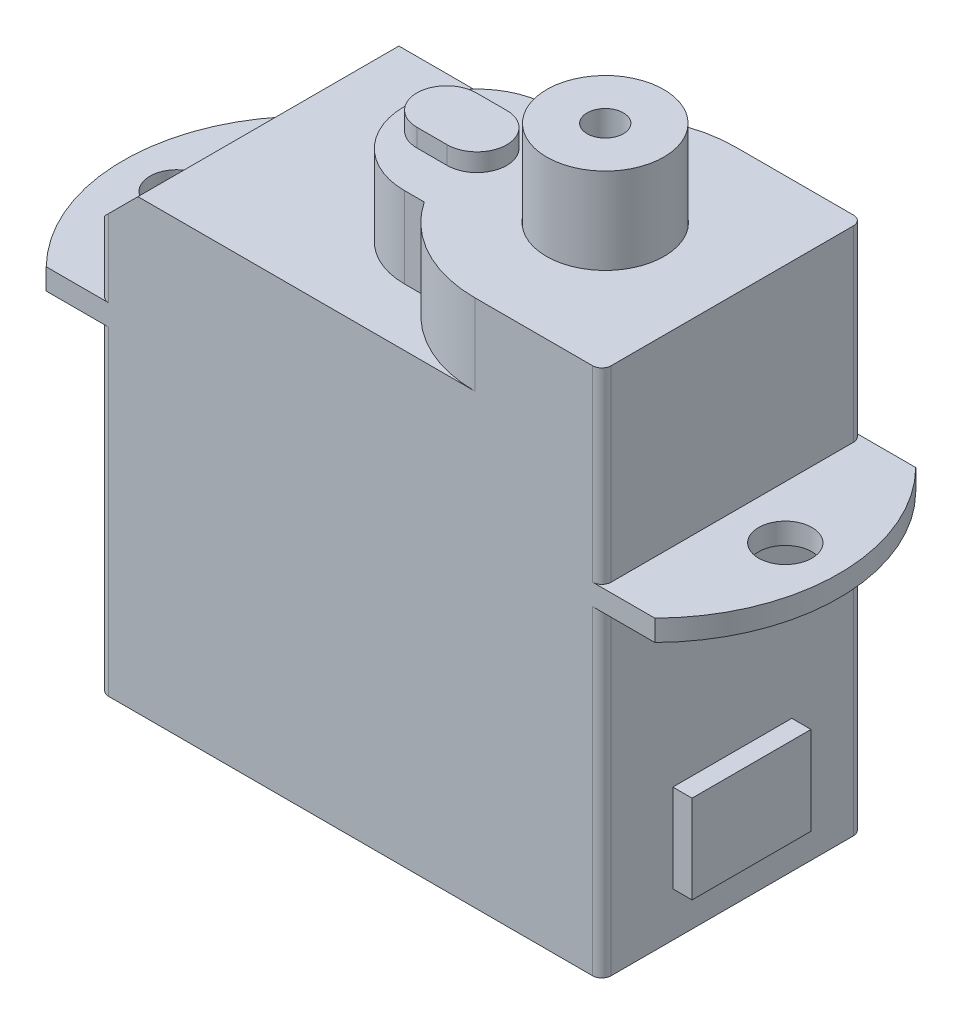
SolidWorks part; units mm, degrees
ref_plane "前视基准面" through (0, 0, 0) normal (0, 0, 1) x (1, 0, 0)
ref_plane "上视基准面" through (0, 0, 0) normal (0, 1, 0) x (1, 0, 0)
ref_plane "右视基准面" through (0, 0, 0) normal (1, 0, 0) x (0, 0, -1)
sketch "草图1" plane through (0, 0, 0) normal (0, 1, 0) x (1, 0, 0)
  line L1 (-8.11, 4.21) -> (8.11, 4.21)
  line L2 (-8.11, 4.21) -> (-8.11, -4.21)
  line L3 (-8.11, -4.21) -> (8.11, -4.21)
  line L4 (8.11, 4.21) -> (8.11, -4.21)
  line L5 (-8.11, 4.21) -> (8.11, -4.21) construction
  line L6 (-8.11, -4.21) -> (8.11, 4.21) construction
  point P0 (0, 0)
  dimension "D1" = 16.22
  dimension "D2" = 8.42
extrude "凸台-拉伸1" add sketch "草图1" along normal blind 11
sketch "草图2" plane through (0, 11, 0) normal (0, 1, 0) x (1, 0, 0)
  line L0 (-11.55, 6.6947) -> (-11.55, -6.3052) construction
  line L1 (-8.11, 4.21) -> (-9.82, 4.21)
  line L2 (-8.11, 4.21) -> (-8.11, -4.21)
  line L3 (-8.11, -4.21) -> (-9.82, -4.21)
  line L4 (-9.82, 4.21) -> (-9.82, -4.21)
  line L5 (8.11, 4.21) -> (9.82, 4.21)
  line L6 (8.11, 4.21) -> (8.11, -4.21)
  line L7 (8.11, -4.21) -> (9.82, -4.21)
  line L8 (9.82, 4.21) -> (9.82, -4.21)
  line L9 (11.55, 6.8827) -> (11.55, -7.7279) construction
  line L10 (0, 6.0541) -> (0, -6.3052) construction
  arc A0 (-9.82, 4.21) -> (-9.82, -4.21) centre (-5.5624, 0) ccw
  arc A1 (9.82, 4.21) -> (9.82, -4.21) centre (5.5624, 0) cw
  circle A2 centre (-9.82, 0) radius 0.86
  circle A3 centre (9.82, 0) radius 0.86
  line M5 (8.11, -4.21) -> (8.11, 4.21)
  line M7 (-8.11, 4.21) -> (-8.11, -4.21)
  dimension "D1" = 1.72
  dimension "D2" = 19.64
  dimension "D3" = 23.1
extrude "凸台-拉伸2" add sketch "草图2" against normal blind 0.68 contours A2 L4 A0 | A2 L4 L3 L1 M7 | A3 L8 L5 L7 M5 | A3 L8 A1 region at (-8.922, 11, 0) region at (-9.906, 11, -2.535) region at (8.922, 11, 0) region at (11.464, 11, 0)
sketch "草图3" plane through (0, 11, 0) normal (0, 1, 0) x (1, 0, 0)
  line L6 (8.11, -4.21) -> (8.11, 4.21)
  line L7 (-8.11, -4.21) -> (8.11, -4.21)
  line L16 (-8.11, 4.21) -> (-8.11, -4.21)
  line L17 (8.11, 4.21) -> (-8.11, 4.21)
  line L18 (8.11, -4.21) -> (8.11, 4.21)
  line L19 (-8.11, -4.21) -> (8.11, -4.21)
  line L20 (-8.11, 4.21) -> (-8.11, -4.21)
  line L21 (8.11, 4.21) -> (-8.11, 4.21)
  dimension "D1" = 0
extrude "凸台-拉伸3" add sketch "草图3" along normal blind 3.44
sketch "草图4" plane through (0, 14.44, 0) normal (0, 1, 0) x (1, 0, 0)
  line L0 (-8.11, -4.21) -> (8.11, -4.21) construction
  line L1 (8.11, 4.21) -> (4.01, 4.21)
  line L2 (8.11, 4.21) -> (8.11, -4.21)
  line L3 (8.11, -4.21) -> (4.01, -4.21)
  line L4 (4.01, 4.21) -> (4.01, -4.21)
  line L5 (4.188, 0) -> (-0.12, 0) construction
  line L6 (-18.1541, 0) -> (19.9236, 0) construction
  line L7 (2.11, 0) -> (2.11, -1.3266) construction
  line L16 (4.188, -2.35) -> (-0.12, -2.35)
  line L17 (4.188, 2.35) -> (-0.12, 2.35)
  arc A0 (4.01, 4.21) -> (4.01, -4.21) centre (4.01, 0) ccw
  arc A1 (4.188, -2.35) -> (4.188, 2.35) centre (4.188, 0) ccw
  circle A2 centre (4.01, 0) radius 1.9
  arc A8 (-0.12, 2.35) -> (-0.12, -2.35) centre (-0.12, 0) ccw
  point P10 (2.034, 0)
  point P20 (-2.47, 0)
  line M10 (8.11, 4.21) -> (-8.11, 4.21)
  line M12 (-8.11, -4.21) -> (8.11, -4.21)
  line M13 (8.11, -4.21) -> (8.11, 4.21)
  dimension "D1" = 10.58
  dimension "D2" = 2.35
  dimension "D3" = 3.8
  dimension "D4" = 6
extrude "凸台-拉伸4" add sketch "草图4" along normal blind 2.61 contours L17 A8 L16 A0 | A2 L4 L17 A0 L16 | L4 A0 L17 | L16 A0 L4 | A1 L16 L4 L17 M12 M13 M10 | A2 L4 L16 A1 L17 region at (8.0163, 14.44, 0) region at (2.6505, 14.44, -3.1102) region at (4.099, 14.44, -2.2966) region at (1.4972, 14.44, 0) region at (-1.0255, 14.44, 0) region at (2.6505, 14.44, 3.1102)
sketch "草图5" plane through (0, 17.05, 0) normal (0, 1, 0) x (1, 0, 0)
  line L0 (-1.11, 0) -> (-0.13, 0) construction
  line L1 (-1.11, 0.96) -> (-0.13, 0.96)
  line L2 (-1.11, -0.96) -> (-0.13, -0.96)
  arc A0 (-1.11, 0.96) -> (-1.11, -0.96) centre (-1.11, 0) ccw
  arc A1 (-0.13, -0.96) -> (-0.13, 0.96) centre (-0.13, 0) ccw
  arc A2 (-0.12, 2.35) -> (-0.12, -2.35) centre (-0.12, 0) ccw construction
  point P3 (-0.62, 0)
  point P8 (-2.07, 0)
  point P9 (0.83, 0)
  point P13 (-2.47, 0)
  dimension "D1" = 2.9
  dimension "D2" = 1.92
  dimension "D3" = 0.4
extrude "凸台-拉伸5" add sketch "草图5" along normal blind 0.58
sketch "草图6" plane through (0, 14.44, 0) normal (0, 1, 0) x (1, 0, 0)
  circle A2 centre (4.01, 0) radius 1.89
  circle A3 centre (4.01, 0) radius 1.89
  dimension "D1" = 0.01
extrude "凸台-拉伸6" add sketch "草图6" along normal blind 5.38
sketch "草图7" plane through (0, 19.82, 0) normal (0, 1, 0) x (1, 0, 0)
  circle A0 centre (4.01, 0) radius 0.585
  circle A1 centre (4.01, 0) radius 1.9 construction
  dimension "D1" = 1.17
extrude "切除-拉伸1" cut sketch "草图7" against normal blind 3.6
fillet "倒角1" radius 1.25 1 edges at (-8.11, 14.44, 0) type face fillet profile chamfer first side face at (-1.2776, 14.44, 0) second side face at (-8.11, 12.72, 0)
fillet "圆角1" radius 0.3 8 edges at (8.11, 5.16, -4.21) (8.11, 14.025, -4.21) (8.11, 14.025, 4.21) (8.11, 5.16, 4.21) (-8.11, 12.095, 4.21) (-8.11, 12.095, -4.21) (-8.11, 5.16, -4.21) (-8.11, 5.16, 4.21)
sketch "草图8" plane through (8.11, 0, 0) normal (1, 0, 0) x (0, 0, -1)
  line L0 (0, 0) -> (0, 7.6823) construction
  line L1 (-1.92, 4.28) -> (1.92, 4.28)
  line L2 (-1.92, 4.28) -> (-1.92, 1.4347)
  line L3 (-1.92, 1.4347) -> (1.92, 1.4347)
  line L4 (1.92, 4.28) -> (1.92, 1.4347)
  line L5 (-3.91, 0) -> (3.91, 0) construction
  dimension "D1" = 4.28
  dimension "D2" = 1.4347
  dimension "D3" = 3.84
extrude "凸台-拉伸7" add sketch "草图8" along normal blind 0.62
sketch "草图9" plane through (8.11, 0, 0) normal (1, 0, 0) x (0, 0, -1)
  line L4 (4.21, 11) -> (-4.21, 11)
  line L5 (-4.21, 11) -> (-4.21, 10.32)
  line L6 (-4.21, 10.32) -> (4.21, 10.32)
  line L7 (4.21, 10.32) -> (4.21, 11)
  line L8 (4.21, 11) -> (-4.21, 11)
  line L9 (-4.21, 11) -> (-4.21, 10.32)
  line L10 (-4.21, 10.32) -> (4.21, 10.32)
  line L11 (4.21, 10.32) -> (4.21, 11)
  dimension "D1" = 0
extrude "切除-拉伸2" [suppressed] cut sketch "草图9" along normal through all
